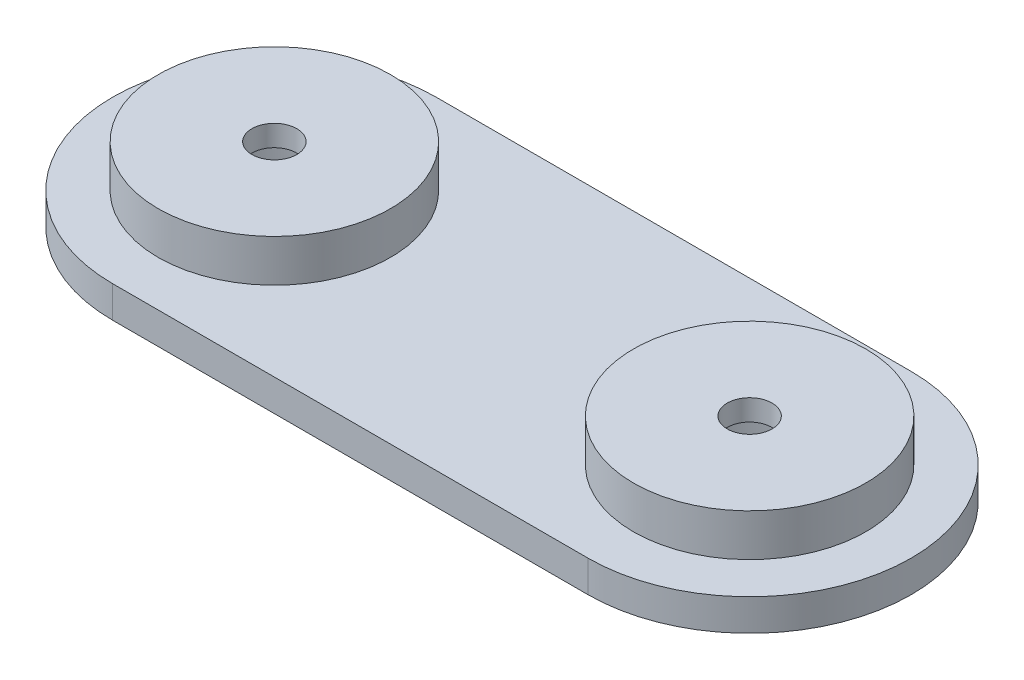
SolidWorks part; units mm, degrees
ref_plane "Front Plane" through (0, 0, 0) normal (0, 0, 1) x (1, 0, 0)
ref_plane "Top Plane" through (0, 0, 0) normal (0, 1, 0) x (1, 0, 0)
ref_plane "Right Plane" through (0, 0, 0) normal (1, 0, 0) x (0, 0, -1)
sketch "Sketch1" plane through (0, 0, 0) normal (0, 1, 0) x (1, 0, 0)
  line L0 (22.5, 0) -> (-22.5, 0)
  line L1 (-22.5, -30.6106) -> (22.5, -30.6106)
  arc A0 (-22.5, 0) -> (-22.5, -30.6106) centre (-22.5, -15.3053) ccw
  arc A1 (22.5, -30.6106) -> (22.5, 0) centre (22.5, -15.3053) ccw
  point P4 (0, 0)
  dimension "D1" = 45
  dimension "D2" = 30.6106
extrude "Boss-Extrude1" add sketch "Sketch1" along normal blind 3
sketch "Sketch2" plane through (0, 3, 0) normal (0, 1, 0) x (1, 0, 0)
  line L0 (-22.5, 0) -> (-22.5, -30.6106) construction
  line L1 (0, 0) -> (0, -30.6106) construction
  line L2 (-22.5, -30.6106) -> (22.5, -30.6106) construction
  circle A0 centre (-22.5, -15.3053) radius 9.75
  circle A2 centre (22.5, -15.3053) radius 9.75
  dimension "D1" = 19.5
extrude "Cut-Extrude1" cut sketch "Sketch2" against normal through all
sketch "Sketch3" plane through (0, 3, 0) normal (0, 1, 0) x (1, 0, 0)
  circle A0 centre (22.5, -15.3053) radius 9.75 construction
  circle A1 centre (22.5, -15.3053) radius 9.75
  circle A2 centre (-22.5, -15.3053) radius 9.75 construction
  circle A3 centre (-22.5, -15.3053) radius 9.75
  circle A4 centre (22.5, -15.3053) radius 11
  circle A5 centre (-22.5, -15.3053) radius 11
  dimension "D1" = 22
extrude "Boss-Extrude2" add sketch "Sketch3" along normal blind 2
sketch "Sketch4" plane through (0, 5, 0) normal (0, 1, 0) x (1, 0, 0)
  circle A0 centre (22.5, -15.3053) radius 11 construction
  circle A1 centre (22.5, -15.3053) radius 11
  circle A2 centre (-22.5, -15.3053) radius 11 construction
  circle A3 centre (-22.5, -15.3053) radius 11
extrude "Boss-Extrude3" add sketch "Sketch4" along normal blind 2
sketch "Sketch5" plane through (0, 7, 0) normal (0, 1, 0) x (1, 0, 0)
  circle A0 centre (22.5, -15.3053) radius 2.125
  circle A1 centre (-22.5, -15.3053) radius 2.125
  dimension "D1" = 4.25
extrude "Cut-Extrude2" cut sketch "Sketch5" against normal blind 2
ref_plane "Plane1" through (0, 1.5, 0) normal (0, -1, 0) x (-1, 0, 0)
mirror "Mirror1" about plane through (0, 1.5, 0) normal (0, -1, 0) of "Boss-Extrude2", "Cut-Extrude2", "Boss-Extrude3"
sketch "Sketch6" plane through (0, -4, 0) normal (0, -1, 0) x (1, 0, 0)
  circle A2 centre (22.5, 15.3053) radius 11 construction
  circle A4 centre (22.5, 15.3053) radius 11
  circle A5 centre (-22.5, 15.3053) radius 11 construction
  circle A7 centre (-22.5, 15.3053) radius 11
extrude "Cut-Extrude3" cut sketch "Sketch6" against normal blind 2
